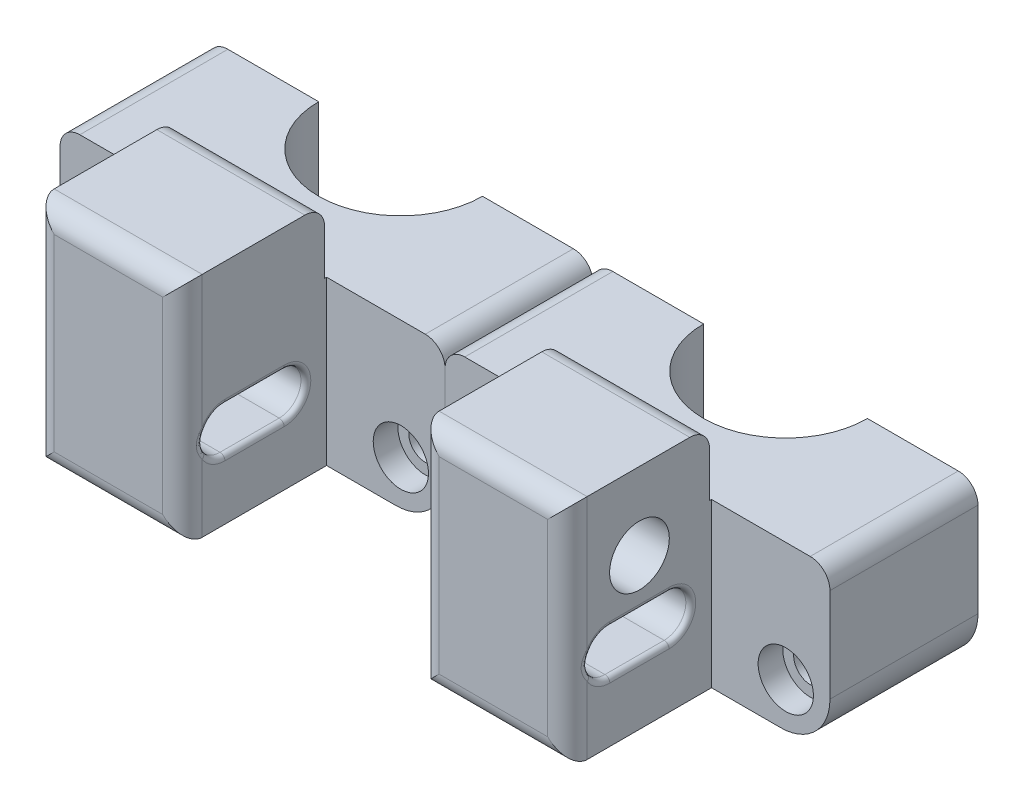
SolidWorks part; units mm, degrees
note: The reader was unsure of these and kept them because the rebuilt part matched: shared geometry of "Sketch11<2>", "Sketch11<3>".
ref_plane "Front Plane" through (0, 0, 0) normal (0, 0, 1) x (1, 0, 0)
ref_plane "Top Plane" through (0, 0, 0) normal (0, 1, 0) x (1, 0, 0)
ref_plane "Right Plane" through (0, 0, 0) normal (1, 0, 0) x (0, 0, -1)
sketch "Sketch1" plane through (0, 0, 0) normal (0, 0, 1) x (1, 0, 0)
  line L6 (-17.3285, -87.5791) -> (-17.3285, -76.0527)
  line L7 (-17.3285, -66.34) -> (-17.3285, -87.5791) construction
  line L8 (-17.3285, -76.0527) -> (21.6715, -76.0527)
  line L9 (21.6715, -87.5791) -> (21.6715, -66.34) construction
  line L10 (21.6715, -76.0527) -> (21.6715, -87.5791)
  line L11 (16.6715, -92.5791) -> (-12.3285, -92.5791)
  arc A2 (-12.3285, -92.5791) -> (-17.3285, -87.5791) centre (-12.3285, -87.5791) cw
  arc A3 (16.6715, -92.5791) -> (21.6715, -87.5791) centre (16.6715, -87.5791) ccw
  circle A4 centre (-12.8517, -88.1023) radius 1.7
  circle A5 centre (17.1948, -88.1023) radius 1.7
  dimension "D1" = 3.4
extrude "Boss-Extrude1" add sketch "Sketch1" along normal blind 15
sketch "Sketch4" plane through (0, -92.5791, 0) normal (0, -1, 0) x (1, 0, 0)
  line L0 (-12.3285, 0) -> (16.6715, 0) construction
  circle A2 centre (2.1715, 0) radius 8.3
extrude "Cut-Extrude1" cut sketch "Sketch4" against normal up to surface (16.5264 mm away) up to face at (2.1715, -76.0527, 7.5)
sketch "Sketch5" plane through (0, 0, 15) normal (0, 0, 1) x (1, 0, 0)
  line L0 (-12.3285, -92.5791) -> (16.6715, -92.5791) construction
  line L1 (9.6715, -92.5791) -> (-5.3285, -92.5791)
  line L2 (9.6715, -92.5791) -> (9.6715, -76.0527)
  line L3 (9.6715, -76.0527) -> (-5.3285, -76.0527)
  line L4 (-5.3285, -92.5791) -> (-5.3285, -76.0527)
  line L5 (21.6715, -76.0527) -> (-17.3285, -76.0527) construction
  line L6 (9.6715, -84.3159) -> (21.6715, -84.3159) construction
  line L7 (21.6715, -87.5791) -> (21.6715, -76.0527) construction
  line L8 (-5.3285, -84.3159) -> (-17.3285, -84.3159) construction
  line L9 (-17.3285, -76.0527) -> (-17.3285, -87.5791) construction
  dimension "D1" = 15
extrude "Boss-Extrude2" add sketch "Sketch5" along normal up to surface (14.6006 mm away)
sketch "Sketch6" plane through (-5.3285, 0, 0) normal (-1, 0, 0) x (0, 0, 1)
  line L0 (25.3003, -84.3159) -> (19.3003, -84.3159) construction
  line L1 (25.3003, -86.5159) -> (19.3003, -86.5159)
  line L2 (25.3003, -82.1159) -> (19.3003, -82.1159)
  line L3 (29.6006, -76.0527) -> (15, -92.5791) construction
  line L4 (29.6006, -92.5791) -> (15, -76.0527) construction
  arc A0 (25.3003, -86.5159) -> (25.3003, -82.1159) centre (25.3003, -84.3159) ccw
  arc A1 (19.3003, -82.1159) -> (19.3003, -86.5159) centre (19.3003, -84.3159) ccw
  point P2 (22.3003, -84.3159)
  dimension "D1" = 2.2
  dimension "D2" = 6
extrude "Cut-Extrude2" cut sketch "Sketch6" against normal up to surface (15 mm away) up to face at (9.6715, -84.3159, 22.3003)
sketch "Sketch7" plane through (0, 0, 15) normal (0, 0, 1) x (1, 0, 0)
  circle A0 centre (17.1948, -88.1023) radius 2.8
  circle A1 centre (-12.8517, -88.1023) radius 2.8
  dimension "D1" = 5.6
extrude "Cut-Extrude3" cut sketch "Sketch7" against normal blind 2.5
sketch "Sketch11" plane through (9.6715, 0, 0) normal (1, 0, 0) x (0, 0, -1)
  line L0 (-29.6006, -76.0527) -> (-29.6006, -92.5791) construction
  line L1 (-15.2, -81.23) -> (-29.6006, -81.23)
  line L2 (-15.2, -81.23) -> (-15.2, -69.5033)
  line L3 (-15.2, -69.5033) -> (-29.6006, -69.5033)
  line L4 (-29.6006, -81.23) -> (-29.6006, -69.5033)
  line L6 (-15.2, -92.5791) -> (-15.2, -69.5033) construction
  line L8 (-30.6006, -69.5033) -> (402.3994, -69.5033) construction
  circle A0 centre (-22.3003, -77.3159) radius 3.025
  line M7 (-15, -76.0527) -> (-29.6006, -76.0527)
  dimension "D1" = 6.05
extrude "Boss-Extrude3" add sketch "Sketch11" against normal up to surface (15 mm away) up to face at (-5.3285, -84.3159, 22.3003)
extrude "Cut-Extrude4" cut sketch "Sketch11<2>" against normal blind 28 contours A0 M7
sketch "Sketch11<2>" plane through (9.6715, 0, 0) normal (1, 0, 0) x (0, 0, -1) same geometry as "Sketch11"
extrude "Boss-Extrude4" add sketch "Sketch11<3>" along normal up to surface (8.7 mm away) from offset 6.3 contours A0 M7 | A0 M7
sketch "Sketch11<3>" plane through (9.6715, 0, 0) normal (1, 0, 0) x (0, 0, -1) same geometry as "Sketch11"
fillet "Fillet1" radius 2 7 edges at (9.6715, -81.0412, 29.6006) (-5.3285, -81.0412, 29.6006) (21.6715, -76.0527, 7.5) (-17.3285, -76.0527, 7.5) (2.1715, -69.5033, 15.2) (2.1715, -69.5033, 29.6006) (2.1715, -92.5791, 29.6006)
fillet "Fillet2" radius 0.5 8 edges at (-5.3285, -86.5159, 22.3003) (-5.3285, -84.3159, 17.1003) (-5.3285, -82.1159, 22.3003) (9.6715, -82.1159, 22.3003) (9.6715, -84.3159, 17.1003) (9.6715, -86.5159, 22.3003) (-5.3285, -84.3159, 27.5003) (9.6715, -84.3159, 27.5003)
mirror "Mirror1" about plane through (-17.3285, -87.5791, 15) normal (1, 0, 0) of bodies 108
